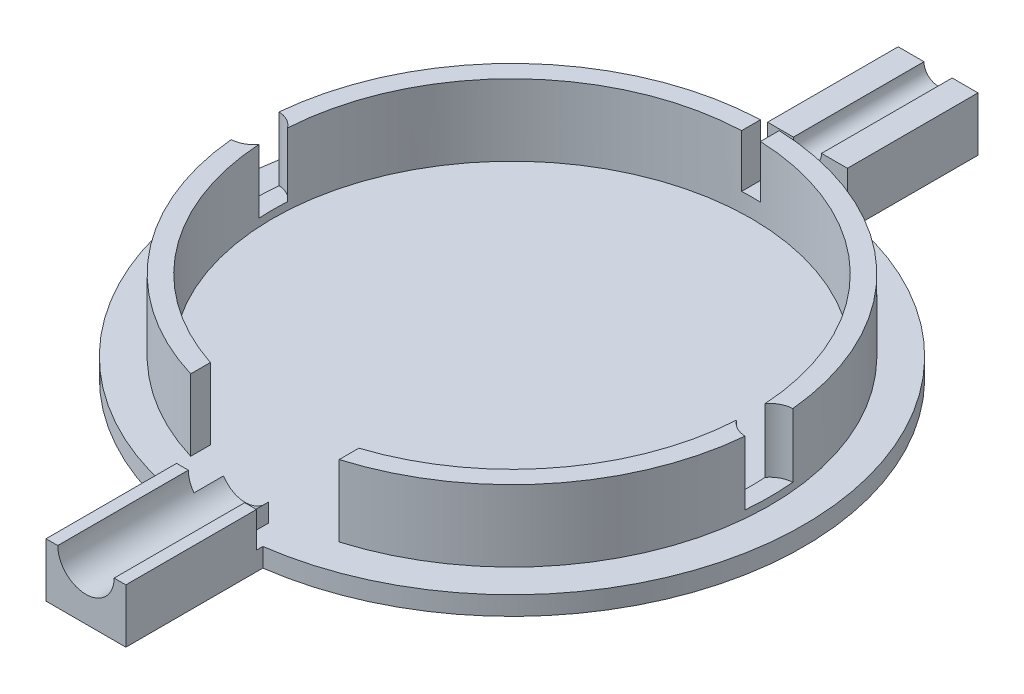
SolidWorks part; units mm, degrees
ref_plane "Front Plane" through (0, 0, 0) normal (0, 0, 1) x (1, 0, 0)
ref_plane "Top Plane" through (0, 0, 0) normal (0, 1, 0) x (1, 0, 0)
ref_plane "Right Plane" through (0, 0, 0) normal (1, 0, 0) x (0, 0, -1)
sketch "Sketch1" plane through (0, 0, 0) normal (0, 1, 0) x (1, 0, 0)
  circle A0 centre (0, 0) radius 31.06
  dimension "D1" = 62.12
extrude "Boss-Extrude1" add sketch "Sketch1" along normal blind 2
sketch "Sketch2" plane through (0, 2, 0) normal (0, 1, 0) x (1, 0, 0)
  circle A0 centre (0, 0) radius 27.46
  circle A1 centre (0, 0) radius 25.46
  circle A2 centre (0, 0) radius 31.06 construction
  dimension "D1" = 2
  dimension "D2" = 3.6
extrude "Boss-Extrude2" add sketch "Sketch2" along normal blind 7.6
sketch "Sketch4" plane through (0, 9.6, 0) normal (0, 1, 0) x (1, 0, 0)
  arc A0 (25.4144, -1.5226) -> (27.3416, -2.5472) centre (27.46, 0) ccw
  circle A1 centre (0, 0) radius 27.46 construction
  arc A2 (-27.3416, -2.5472) -> (-25.4144, -1.5226) centre (-27.46, 0) ccw
  circle A3 centre (0, 0) radius 25.46 construction
  arc A4 (-25.4144, 1.5226) -> (-25.4144, -1.5226) centre (0, 0) ccw
  arc A5 (-27.3416, 2.5472) -> (-27.3416, -2.5472) centre (0, 0) ccw
  arc A6 (25.4144, -1.5226) -> (25.4144, 1.5226) centre (0, 0) ccw
  arc A7 (27.3416, -2.5472) -> (27.3416, 2.5472) centre (0, 0) ccw
  arc A8 (-25.4144, 1.5226) -> (-27.3416, 2.5472) centre (-27.46, 0) ccw
  arc A9 (27.3416, 2.5472) -> (25.4144, 1.5226) centre (27.46, 0) ccw
  circle M1 centre (0, 0) radius 27.46
  circle M2 centre (0, 0) radius 25.46
  dimension "D1" = 5.1
  dimension "D2" = 5.1
extrude "Cut-Extrude1" cut sketch "Sketch4" against normal blind 6.8 contours A9 A0 M1 M2 | A4 A2 A5 A8 region at (26.5014, 9.6, 0)
sketch "Sketch5" plane through (0, 9.6, 0) normal (0, 1, 0) x (1, 0, 0)
  line L0 (0, -25.46) -> (0, -27.46)
  line L1 (3, -25.2826) -> (3, -27.2956)
  line L2 (-3, -25.2826) -> (-3, -27.2956)
  line L3 (3, -25.46) -> (3, -27.46) construction
  line L4 (-3, -25.46) -> (-3, -27.46) construction
  arc A0 (-25.4144, -1.5226) -> (25.4144, -1.5226) centre (0, 0) ccw construction
  arc A1 (-27.3416, -2.5472) -> (27.3416, -2.5472) centre (0, 0) ccw construction
  arc A3 (-3, -25.2826) -> (3, -25.2826) centre (0, 0) ccw
  arc A4 (-3, -27.2956) -> (3, -27.2956) centre (0, 0) ccw
  arc M2 (-27.3416, -2.5472) -> (27.3416, -2.5472) centre (0, 0) ccw
  arc M4 (25.4144, -1.5226) -> (-25.4144, -1.5226) centre (0, 0) cw
  dimension "D1" = 3
  dimension "D2" = 3
extrude "Cut-Extrude2" cut sketch "Sketch5" against normal blind 6.8 contours L2 L0 M4 M2 | L1 L0 M4 M2 region at (1.5016, 9.6, 26.403) region at (-1.5016, 9.6, 26.403)
sketch "Sketch7" plane through (0, 2, 0) normal (0, 1, 0) x (1, 0, 0)
  line L2 (2.4, -28.3014) -> (2.4, -30.9671)
  line L3 (-2.4, -28.3014) -> (-2.4, -30.9671)
  line L4 (3, -25.2826) -> (3, -27.2956) construction
  circle A0 centre (0, 0) radius 31.06 construction
  arc A1 (-2.4, -30.9671) -> (2.4, -30.9671) centre (0, 0) ccw
  arc A4 (-2.4, -28.3014) -> (2.4, -28.3014) centre (0, 0.0572) ccw
  dimension "D1" = 4.8
  dimension "D2" = 0.6
extrude "Boss-Extrude5" add sketch "Sketch7" along normal blind 7.6
ref_plane "Plane1" through (0, 0, 31.06) normal (0, 0, 1) x (1, 0, 0)
sketch "Sketch8" plane through (0, 0, 31.06) normal (0, 0, 1) x (1, 0, 0)
  line L0 (2.4, 9.6) -> (-2.4, 9.6) construction
  line L1 (2.4, 9.6) -> (-2.4, 9.6)
  line L2 (31.06, 2) -> (-31.06, 2) construction
  line L3 (2.4, 2) -> (-2.4, 2)
  line L4 (2.4, 9.6) -> (2.4, 2) construction
  line L5 (2.4, 9.6) -> (2.4, 2)
  line L6 (-2.4, 9.6) -> (-2.4, 2) construction
  line L7 (-2.4, 9.6) -> (-2.4, 2)
  line L8 (-2.4, 5.75) -> (2.4, 5.75)
  circle A0 centre (0, 5.75) radius 3
  dimension "D2" = 6
  dimension "D1" = 3.75
extrude "Cut-Extrude3" cut sketch "Sketch8" against normal blind 7.6 contours L7 A0 L5 L8 | L5 A0 L7 L8 | A0 L5 L1 L7 region at (0, 8.9459, 31.06) region at (0, 7.0916, 31.06) region at (0, 4.4084, 31.06)
sketch "Sketch9" plane through (0, 0, 0) normal (0, 0, 1) x (1, 0, 0)
  line L0 (25.4144, 9.6) -> (-25.4144, 9.6) construction
  line L1 (-1, 4) -> (1, 4)
  line L2 (-1, 4) -> (-1, 9.6)
  line L3 (-1, 6) -> (1, 6)
  line L4 (1, 4) -> (1, 9.6)
  line L5 (-1, 4) -> (1, 6) construction
  line L6 (-1, 6) -> (1, 4) construction
  line L7 (1, 9.6) -> (-1, 9.6)
  point P0 (0, 5)
  dimension "D1" = 5
  dimension "D2" = 2
  dimension "D3" = 2
extrude "Cut-Extrude4" cut sketch "Sketch9" against normal through all contours L1 L4 L3 L2 | L4 L7 L2 L3 region at (0, 5, 0) region at (0, 7.8, 0)
sketch "Sketch11" plane through (0, 9.6, 0) normal (0, 1, 0) x (1, 0, 0)
  line L2 (-7.9, -27.9874) -> (7.9, -27.9874)
  line L4 (7.9, -24.1658) -> (-7.9, -24.1658)
  line L5 (7.9, -24.1658) -> (7.9, -28.7542)
  line L6 (7.9, -28.7542) -> (-7.9, -28.7542)
  line L7 (-7.9, -24.1658) -> (-7.9, -28.7542)
  line L8 (7.9, -24.1658) -> (-7.9, -28.7542) construction
  line L9 (7.9, -28.7542) -> (-7.9, -24.1658) construction
  arc A2 (3, -25.2826) -> (25.4144, -1.5226) centre (0, 0) ccw construction
  arc A3 (3, -25.2826) -> (25.4144, -1.5226) centre (0, 0) ccw
  point P7 (0, -26.46)
  line M1 (-3, -27.2956) -> (-3, -25.2826)
  arc M2 (-3, -25.2826) -> (-25.4144, -1.5226) centre (0, 0) cw
  arc M4 (-27.3416, -2.5472) -> (-3, -27.2956) centre (0, 0) ccw
  dimension "D1" = 15.8
extrude "Cut-Extrude5" cut sketch "Sketch11" against normal up to surface (7.6 mm away) contours A3 | L4 L7 L2 L5 M2 M1 M4 | L7 M2 M4 M1 region at (1.0892, 9.6, 26.1222) region at (-5.4664, 9.6, 25.8478) up to face at (0, 2, 27.46)
sketch "Sketch12" plane through (0, 0, 0) normal (0, -1, 0) x (1, 0, 0)
  line L0 (0, 31.06) -> (0, 45.35)
  line L1 (-4.25, 31.06) -> (4.25, 31.06)
  line L2 (4.25, 30.7679) -> (4.25, 45.35)
  line L3 (-4.25, 30.7679) -> (-4.25, 45.35)
  line L4 (-4.25, 45.35) -> (4.25, 45.35)
  line L5 (5.5481, 0) -> (-4.25, 0)
  line L6 (-14.4841, 45.35) -> (8.5, 45.35) construction
  line L7 (-14.4841, 31.06) -> (8.5, 31.06) construction
  line L8 (-4.25, -45.35) -> (4.25, -45.35)
  line L9 (-4.25, -30.7679) -> (-4.25, -45.35)
  line L10 (4.25, -30.7679) -> (4.25, -45.35)
  line L11 (-4.25, -31.06) -> (4.25, -31.06)
  line L12 (0, -31.06) -> (0, -45.35)
  circle A0 centre (0, 0) radius 31.06 construction
  circle A1 centre (0, 0) radius 31.06
  point P6 (4.25, 0)
  point P8 (-4.25, 0)
  circle M1 centre (0, 0) radius 31.06
  dimension "D1" = 14.29
  dimension "D5" = 14.29
extrude "Boss-Extrude7" add sketch "Sketch12" against normal blind 2 contours L4 L0 L1 L2 | L4 L3 L1 L0 | L2 L1 M1 | L3 L1 M1 | L11 L12 L8 L10 | L12 L11 L9 L8 | L9 L11 M1 | L11 L10 M1 region at (-2.125, 0, 38.205) region at (-3.1885, 0, 30.9724) region at (2.125, 0, 38.205) region at (3.1885, 0, 30.9724) region at (-3.1885, 0, -30.9724) region at (3.1885, 0, -30.9724) region at (-2.125, 0, -38.205) region at (2.125, 0, -38.205)
sketch "Sketch13" plane through (0, 0, 45.35) normal (0, 0, 1) x (1, 0, 0)
  line L0 (-4.25, 2) -> (4.25, 2) construction
  line L1 (-4.25, 2) -> (4.25, 2)
  line L2 (-3, 5.75) -> (-4.25, 5.75)
  line L3 (4.25, 2) -> (-4.25, 2)
  line L4 (4.25, 2) -> (4.25, 5.75)
  line L5 (4.25, 5.75) -> (3, 5.75)
  line L6 (-4.25, 2) -> (-4.25, 5.75)
  arc A0 (-3, 5.75) -> (3, 5.75) centre (0, 5.75) ccw
  dimension "D2" = 6
  dimension "D1" = 3.75
extrude "Boss-Extrude8" add sketch "Sketch13" against normal blind 13.9 contours L3 L6 L2 A0 L5 L4
sketch "Sketch14" plane through (0, 0, 31.06) normal (0, 0, 1) x (1, 0, 0)
  line L3 (-2.4, 2) -> (2.4, 2)
  line L4 (2.4, 2) -> (2.4, 3.95)
  line L5 (-2.4, 3.95) -> (-2.4, 2)
  line L6 (-2.4, 2) -> (2.4, 2)
  line L7 (2.4, 2) -> (2.4, 3.95)
  line L8 (-2.4, 3.95) -> (-2.4, 2)
  arc A1 (-2.4, 3.95) -> (2.4, 3.95) centre (0, 5.75) ccw
  arc A2 (-2.4, 3.95) -> (2.4, 3.95) centre (0, 5.75) ccw
  dimension "D1" = 0
extrude "Boss-Extrude9" add sketch "Sketch14" along normal blind 2 and the other way blind 2
sketch "Sketch15" plane through (0, 0, -45.35) normal (0, 0, -1) x (-1, 0, 0)
  line L0 (-1.5, 5.75) -> (-4.25, 5.75)
  line L1 (4.25, 0) -> (-4.25, 0)
  line L2 (4.25, 0) -> (4.25, 5.75)
  line L3 (4.25, 5.75) -> (1.5, 5.75)
  line L4 (-4.25, 0) -> (-4.25, 5.75)
  arc A0 (-1.5, 5.75) -> (1.5, 5.75) centre (0, 5.75) ccw
  dimension "D2" = 3
  dimension "D1" = 5.75
extrude "Boss-Extrude10" add sketch "Sketch15" against normal blind 13.9
